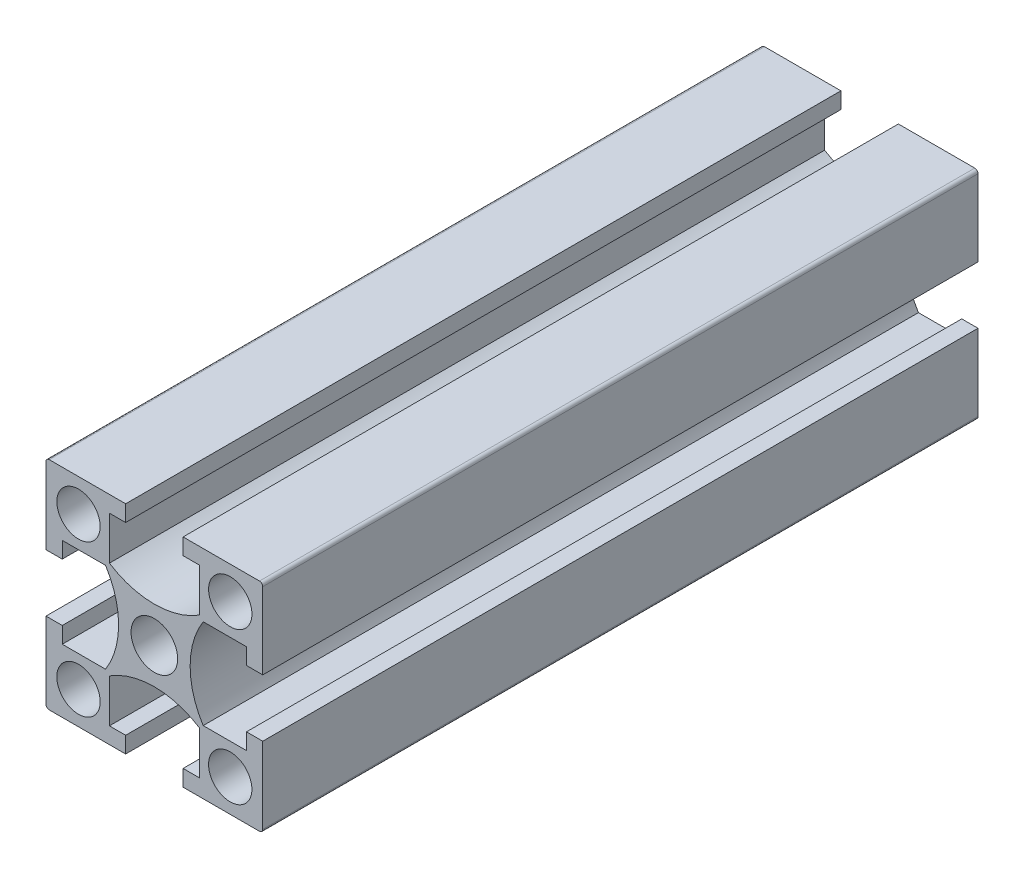
SolidWorks part; units mm, degrees
material "3.0255 (EN-AW 1350A)"
ref_plane "정면" through (0, 0, 0) normal (0, 0, 1) x (1, 0, 0)
ref_plane "윗면" through (0, 0, 0) normal (0, 1, 0) x (1, 0, 0)
ref_plane "우측면" through (0, 0, 0) normal (1, 0, 0) x (0, 0, -1)
sketch "스케치1" plane through (0, 0, 0) normal (0, 0, 1) x (1, 0, 0)
  line L0 (0, 32.0265) -> (0, -31.6588) construction
  line L1 (-10, 10) -> (-10, -10)
  line L2 (-10, 10) -> (10, 10)
  line L3 (-10, 2.65) -> (-8.5, 2.65)
  line L4 (13.6618, 0) -> (-11.6993, 0) construction
  line L5 (-8.5, 2.65) -> (-8.5, 4.15)
  line L6 (-8.5, 4.15) -> (-4.5032, 4.15)
  line L7 (-10, -2.65) -> (-8.5, -2.65)
  line L8 (-8.5, -2.65) -> (-8.5, -4.15)
  line L9 (-8.5, -4.15) -> (-4.5032, -4.15)
  line L10 (-10, -10) -> (10, -10)
  line L11 (10, 10) -> (10, -10)
  circle A0 centre (-7, 7) radius 2
  circle A1 centre (-7, -7) radius 2
  arc A2 (-4.5032, 4.15) -> (-4.5032, -4.15) centre (-11.0587, 0) cw
  circle A3 centre (0, 0) radius 2.15
  circle A4 centre (7, 7) radius 2
  circle A5 centre (7, -7) radius 2
  point P21 (-10, 0)
  point P23 (-3.3, 0)
  point P31 (0, -10)
  point P32 (0, 10)
  dimension "D3" = 4
  dimension "D9" = 6.7
  dimension "D10" = 4.3
  dimension "D11" = 7.7587
  dimension "D1" = 20
  dimension "D2" = 20
  dimension "D4" = 14
  dimension "D5" = 14
  dimension "D6" = 5.3
  dimension "D7" = 8.3
  dimension "D8" = 1.5
extrude "보스-돌출1" add sketch "스케치1" along normal blind 66 contours A0 | A4 | A3 | A5 | A1 | A2 L6 L5 L3 L1 L7 L8 L9 | L2 L11 L10 L1 region at (-6.6069, 0, 0) region at (-7, 7, 0) region at (-7, -7, 0) region at (0, 0, 0) region at (7, 7, 0) region at (7, -7, 0)
extrude "컷-돌출1" cut sketch "스케치1<3>" along normal up to next contours A2 L6 L5 L3 L1 L7 L8 L9 region at (-6.6069, 0, 0)
sketch "스케치1<3>" plane through (0, 0, 0) normal (0, 0, 1) x (1, 0, 0) same geometry as "스케치1"
pattern_circular "원형 패턴1" count 4 over 360 about axis through (0, 0, 66) along (0, 0, -1) of "컷-돌출1" reverse direction yes
fillet "필렛1" radius 0.3 4 edges at (10, -10, 33) (-10, -10, 33) (-10, 10, 33) (10, 10, 33)
sketch "스케치3" plane through (0, 10, 0) normal (0, 1, 0) x (1, 0, 0)
  line L0 (4.15, 0) -> (-4.15, 0) construction
  line L1 (-4.15, -66) -> (4.15, -66) construction
  circle A0 centre (0, -10) radius 2.15
  circle A1 centre (0, -55) radius 2.5
  dimension "D1" = 10
  dimension "D2" = 11
  dimension "D3" = 4.3
extrude "컷-돌출2" cut sketch "스케치3" against normal through all
sketch "스케치4" plane through (0, 10, 0) normal (0, 1, 0) x (1, 0, 0)
  line L0 (4.15, 0) -> (-4.15, 0) construction
  circle A0 centre (0, -19) radius 2.5
  dimension "D1" = 19
extrude "컷-돌출3" cut sketch "스케치4" against normal through all
